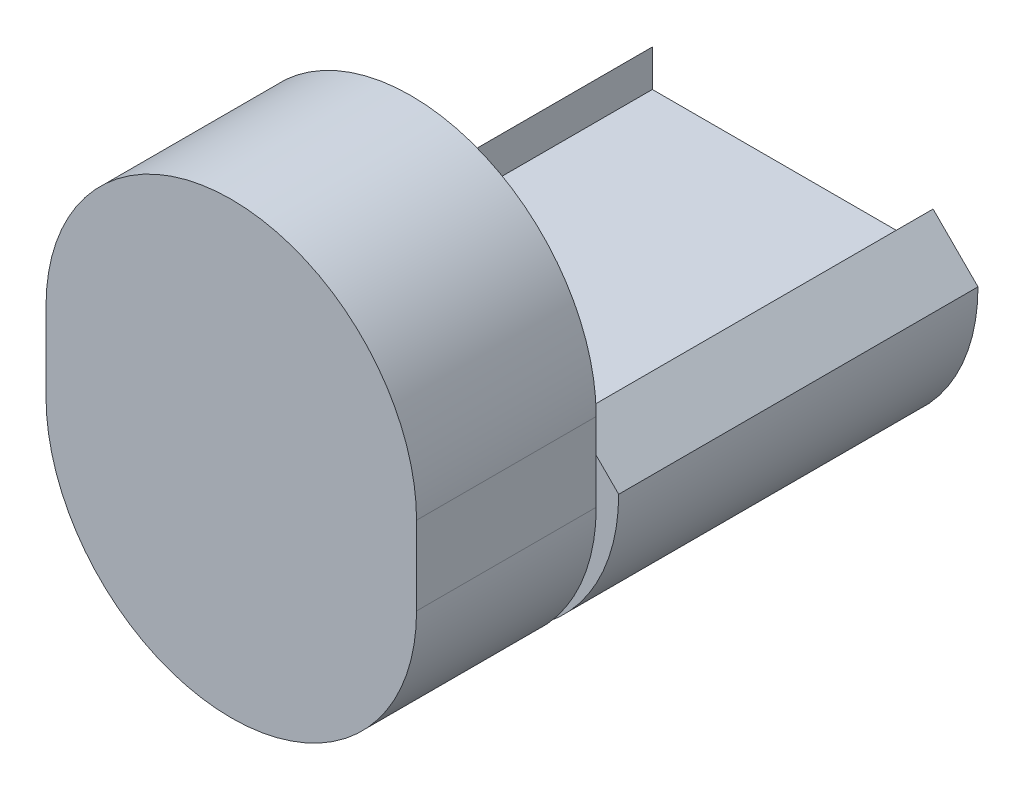
SolidWorks part; units mm, degrees
ref_plane "Front Plane" through (0, 0, 0) normal (0, 0, 1) x (1, 0, 0)
ref_plane "Top Plane" through (0, 0, 0) normal (0, 1, 0) x (1, 0, 0)
ref_plane "Right Plane" through (0, 0, 0) normal (1, 0, 0) x (0, 0, -1)
sketch "Sketch2" plane through (0, 0, 0) normal (0, 0, 1) x (1, 0, 0)
  line L2 (-55.5625, -10.3188) -> (-55.5625, 10.3187)
  line L4 (55.5625, -10.3187) -> (55.5625, 10.3188)
  line L5 (-55.5625, -10.3188) -> (55.5625, 10.3188) construction
  line L6 (-55.5625, 10.3187) -> (55.5625, -10.3187) construction
  arc A0 (-55.5625, 10.3187) -> (55.5625, 10.3188) centre (0, 10.3187) cw
  arc A1 (55.5625, -10.3187) -> (-55.5625, -10.3188) centre (0, -10.3188) cw
  point P0 (0, 0)
  point P7 (0, 65.8812)
  point P8 (0, -65.8813)
  point P10 (0, 0)
  point P11 (0, -25.9771)
  point P12 (0, -26.4047)
  point P13 (0, 0)
  dimension "D1" = 111.125
  dimension "D2" = 131.7625
sketch "Sketch1" plane through (0, 0, 0) normal (0, 0, 1) x (1, 0, 0)
  line L0 (-39.6875, -2.6352) -> (39.6875, -2.6352)
  line L1 (-39.6875, -2.6352) -> (-39.6875, 7.7788)
  line L2 (-39.6875, 7.7788) -> (-52.3875, -4.9212)
  line L3 (39.6875, -2.6352) -> (39.6875, 7.7788)
  line L4 (39.6875, 7.7788) -> (52.3875, -4.9212)
  line L5 (-52.3875, -4.9212) -> (-52.3875, 78.4383) construction
  line L6 (52.3875, -4.9212) -> (52.3875, 84.9615) construction
  circle A0 centre (0, 29.21) radius 28.575
  arc A1 (-52.3875, -4.9212) -> (52.3875, -4.9212) centre (0, -4.9212) ccw
  circle A2 centre (0, 29.21) radius 33.3375 construction
  point P5 (0, -2.6352)
  point P12 (0, 0)
  point P13 (0, 26.5112)
  point P15 (0, 0)
  point P16 (0, 26.5112)
  point P17 (0, 0)
  point P19 (0, 29.5582)
  point P20 (0, 29.2271)
  dimension "D1" = 57.15
  dimension "D2" = 66.675
  dimension "D3" = 12.7
  dimension "D4" = 45
  dimension "D6" = 10.414
  dimension "D7" = 31.8452
  dimension "D8" = 29.21
  dimension "D5" = 79.375
extrude "Boss-Extrude1" add sketch "Sketch1" along normal blind 101.6 contours A1 L4 L3 L0 L1 L2
sketch "Sketch4" plane through (0, 0, 0) normal (0, 0, 1) x (1, 0, 0)
  circle A0 centre (0, 29.21) radius 28.575
  circle A1 centre (0, 29.21) radius 28.575 construction
ref_plane "Plane1" through (0, 0, 158.75) normal (0, 0, 1) x (1, 0, 0)
ref_axis "Axis1" through (0, 29.21, 0) along (0, 0, 1)
sketch "Sketch3" plane through (0, 0, 158.75) normal (0, 0, 1) x (1, 0, 0)
  line L0 (-52.3875, -4.9212) -> (-52.3875, 17.3038)
  line L1 (52.3875, -4.9212) -> (52.3875, 17.3038)
  arc A0 (-52.3875, -4.9212) -> (52.3875, -4.9212) centre (0, -4.9212) ccw
  arc A1 (-52.3875, -4.9212) -> (52.3875, -4.9212) centre (0, -4.9212) ccw construction
  arc A2 (-52.3875, 17.3038) -> (52.3875, 17.3038) centre (0, 17.3038) cw
  point P10 (0, 69.6913)
  point P11 (0, -57.3087)
  dimension "D1" = 127
extrude "Boss-Extrude2" add sketch "Sketch3" against normal blind 50.8 separate body
sketch "Sketch6" plane through (0, 0, 0) normal (1, 0, 0) x (0, 0, -1)
  line L0 (-131.704, 69.6913) -> (-107.95, 70.485)
  line L1 (-107.95, 69.6913) -> (-158.75, 69.6913) construction
  line L2 (-107.95, 17.3038) -> (-107.95, 69.6913) construction
  line L3 (0, 29.21) -> (-68.0102, 29.21) construction
  dimension "D1" = 41.275
sketch "Sketch7" plane through (0, 0, 158.75) normal (0, 0, 1) x (1, 0, 0)
  circle A0 centre (0, 29.21) radius 44.45
  dimension "D1" = 88.9
equation "\"D1@Sketch2\"=4+3/8"
equation "\"D2@Sketch2\"=5+3/16"
equation "\"D2@Sketch1\"=2+5/8"
equation "\"D1@Boss-Extrude2\"=1+1/8"
